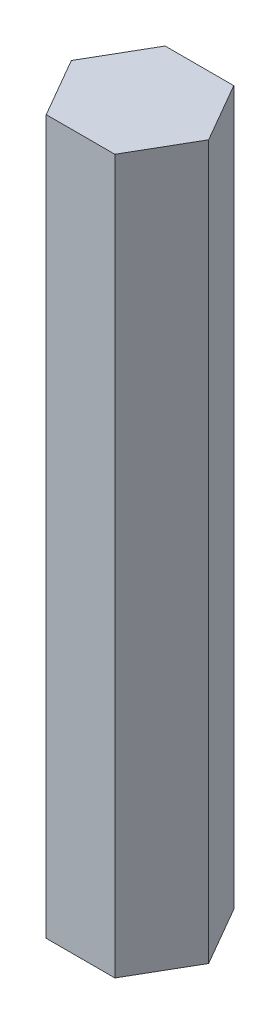
SolidWorks part; units mm, degrees
ref_plane "Front" through (0, 0, 0) normal (0, 0, 1) x (1, 0, 0)
ref_plane "Top" through (0, 0, 0) normal (0, 1, 0) x (1, 0, 0)
ref_plane "Right" through (0, 0, 0) normal (1, 0, 0) x (0, 0, -1)
sketch "Sketch1" plane through (0, 0, 0) normal (0, 1, 0) x (1, 0, 0)
  line L1 (7.3323, 0) -> (3.6662, 6.35)
  line L2 (3.6662, 6.35) -> (-3.6662, 6.35)
  line L3 (-3.6662, 6.35) -> (-7.3323, 0)
  line L4 (-7.3323, 0) -> (-3.6662, -6.35)
  line L5 (-3.6662, -6.35) -> (3.6662, -6.35)
  line L6 (3.6662, -6.35) -> (7.3323, 0)
  circle A0 centre (0, 0) radius 6.35 construction
  dimension "D1" = 12.7
extrude "Boss-Extrude1" add sketch "Sketch1" along normal blind 76.2
ref_axis "Axis1" through (0, 50, 0) along (0, -1, 0)
